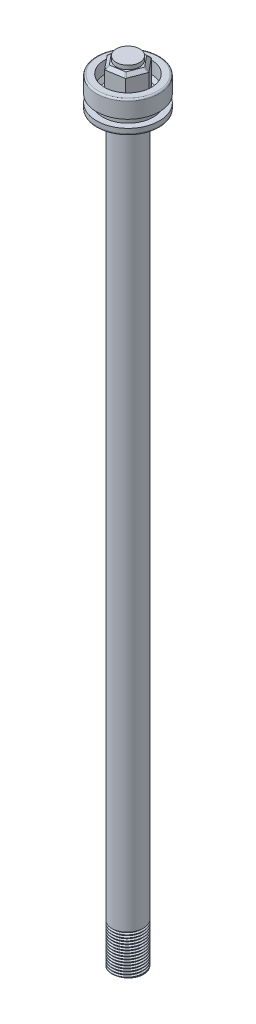
SolidWorks part; units mm, degrees
ref_plane "Front" through (0, 0, 0) normal (0, 0, 1) x (1, 0, 0)
ref_plane "Top" through (0, 0, 0) normal (0, 1, 0) x (1, 0, 0)
ref_plane "Right" through (0, 0, 0) normal (1, 0, 0) x (0, 0, -1)
sketch "Sketch1" plane through (0, 0, 0) normal (0, 1, 0) x (1, 0, 0)
  circle A0 centre (0, 0) radius 25.4
  dimension "D1" = 50.8
extrude "Boss-Extrude1" add sketch "Sketch1" along normal blind 25.4
sketch "Sketch2" plane through (0, 25.4, 0) normal (0, 1, 0) x (1, 0, 0)
  circle A0 centre (0, 0) radius 19.05
  dimension "D1" = 38.1
extrude "Cut-Extrude1" cut sketch "Sketch2" against normal blind 12.7
sketch "Sketch3" plane through (0, 25.4, 0) normal (0, 1, 0) x (1, 0, 0)
  circle A0 centre (0, 0) radius 20.32
  circle A1 centre (0, 0) radius 25.4
  dimension "D1" = 50.8
  dimension "D2" = 40.64
extrude "Cut-Extrude2" cut sketch "Sketch3" against normal blind 6.35 from offset 13.97 offset against normal yes
sketch "Sketch4" plane through (0, 12.7, 0) normal (0, 1, 0) x (1, 0, 0)
  line L1 (-14.4707, -2.3775) -> (-5.1764, -13.7207)
  line L2 (-5.1764, -13.7207) -> (9.2943, -11.3432)
  line L3 (9.2943, -11.3432) -> (14.4707, 2.3775)
  line L4 (14.4707, 2.3775) -> (5.1764, 13.7207)
  line L5 (5.1764, 13.7207) -> (-9.2943, 11.3432)
  line L6 (-9.2943, 11.3432) -> (-14.4707, -2.3775)
  circle A0 centre (0, 0) radius 12.7 construction
  dimension "D1" = 25.4
extrude "Boss-Extrude2" add sketch "Sketch4" along normal blind 22.225
sketch "Sketch5" plane through (0, 34.925, 0) normal (0, 1, 0) x (1, 0, 0)
  circle A0 centre (0, 0) radius 9.525
  dimension "D1" = 19.05
extrude "Boss-Extrude3" add sketch "Sketch5" along normal blind 3.175
sketch "Sketch6" plane through (0, 0, 0) normal (0, -1, 0) x (1, 0, 0)
  circle A0 centre (0, 0) radius 12.7
  dimension "D1" = 25.4
extrude "Boss-Extrude4" add sketch "Sketch6" along normal blind 600
thread "Thread1" pitch 2.1167 method cut profile "Thread Profile1" start angle 0, offset 2.54, length 34.29, pitch 2.1167, diameter 25.4
ref_plane "Plane1" through (12.7, -602.54, 0) normal (0, 0, 1) x (1, 0, 0)
sketch "Thread Profile1" plane through (12.7, -602.54, 0) normal (0, 0, 1) x (1, 0, 0)
  line L0 (0, 0) -> (0, 2.1167) construction
  line L11 (0, 0) -> (0, 1.8521)
  line L12 (0, 1.8521) -> (-1.1457, 1.1906)
  line L13 (-1.1457, 1.1906) -> (-1.1457, 0.6615)
  line L15 (-1.1457, 0.6615) -> (0, 0)
  line L17 (-1.1457, 0.926) -> (0, 0.926) construction
  point P2 (0, 0)
  dimension "Pitch" = 2.1167
  dimension "Profile_Angle" = 60
  dimension "Profile_Land" = 0.5292
  dimension "Profile_Height" = 1.1457
chamfer "Chamfer1" distance 2.54 angle 45 7 edges at (11.8825, 34.925, 4.4829) (2.059, 34.925, 12.532) (-9.8235, 34.925, 8.0491) (-11.8825, 34.925, -4.4829) (9.8235, 34.925, -8.0491) (-2.059, 34.925, -12.532) (0, 12.7, 19.05)
fillet "Fillet2" radius 1.27 8 edges at (13.0236, 33.655, -2.1397) (4.6587, 33.655, -12.3487) (-8.3649, 33.655, -10.2089) (-13.0236, 33.655, 2.1397) (8.3649, 33.655, 10.2089) (0, 25.4, 25.4) (-4.6587, 33.655, 12.3487) (0, 0, 25.4)
